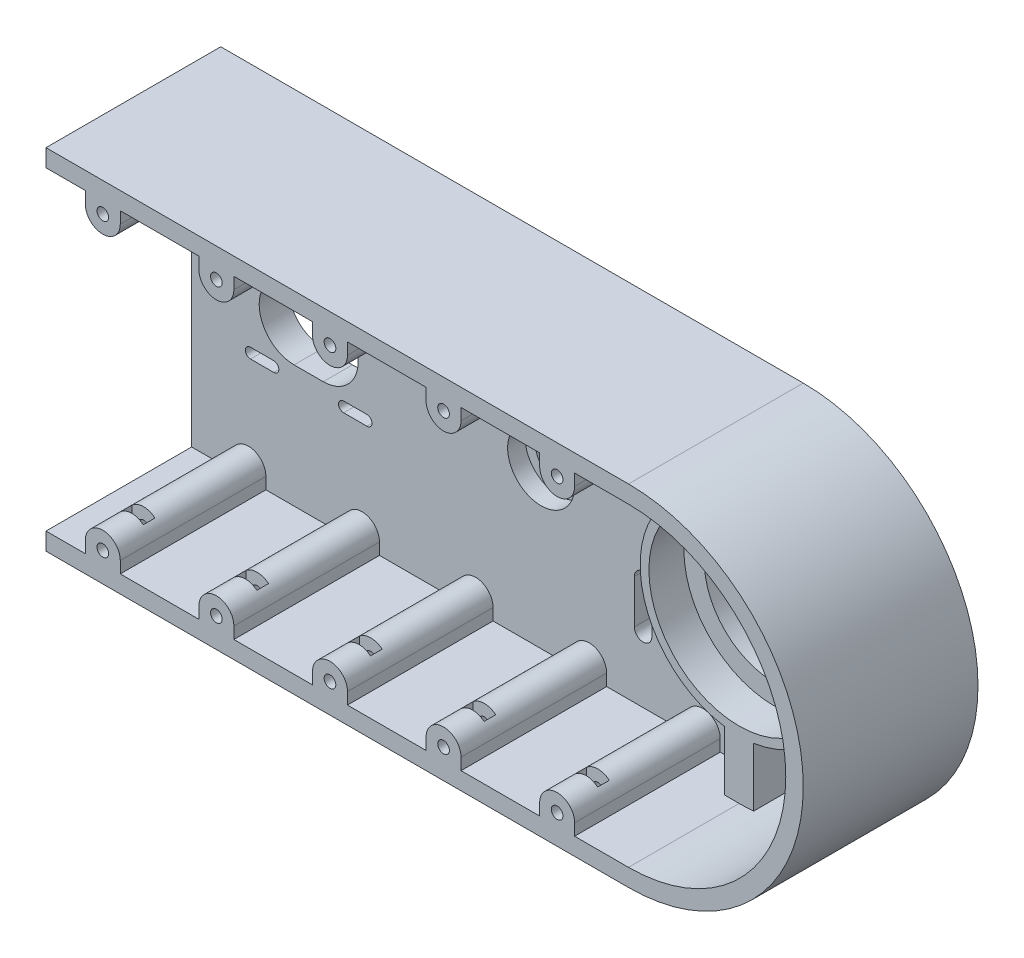
SolidWorks part; units mm, degrees
other "Marcação1"
sketch "Esboço6" plane through (60, -60, 0) normal (0.0064, -0.8941, -0.4477) x (-0.9984, -0.0306, 0.047)
sketch "Esboço8" plane through (60, -60, 0) normal (0.0064, -0.8941, -0.4477) x (-0.9984, -0.0306, 0.047)
sketch "Esboço13" plane through (60, -60, 0) normal (0.0064, -0.8941, -0.4477) x (-0.9984, -0.0306, 0.047)
sketch "Esboço15" plane through (60, -60, 0) normal (0.0064, -0.8941, -0.4477) x (-0.9984, -0.0306, 0.047)
ref_plane "Plano frontal" through (0, 0, 0) normal (0, 0, 1) x (1, 0, 0)
ref_plane "Plano superior" through (0, 0, 0) normal (0, 1, 0) x (1, 0, 0)
ref_plane "Plano direito" through (0, 0, 0) normal (1, 0, 0) x (0, 0, -1)
sketch "Esboço2" plane through (0, 0, 0) normal (0, 0, 1) x (1, 0, 0)
  line L0 (0, 60) -> (-200, 60)
  line L1 (-200, 60) -> (-200, -60)
  line L2 (-200, -60) -> (0, -60)
  circle A0 centre (0, 0) radius 19
  arc A1 (0, -60) -> (0, 60) centre (0, 0) ccw
  dimension "D1" = 38
  dimension "D2" = 120
  dimension "D3" = 200
extrude "Ressalto-extrusão1" add sketch "Esboço2" along normal blind 10
sketch "Esboço3" plane through (0, 0, 10) normal (0, 0, 1) x (1, 0, 0)
  circle A0 centre (0, 0) radius 24
  dimension "D1" = 48
extrude "Corte-extrusão1" cut sketch "Esboço3" against normal blind 7
sketch "Esboço4" plane through (0, 0, 10) normal (0, 0, 1) x (1, 0, 0)
  circle A0 centre (0, 0) radius 31
  circle A1 centre (0, 0) radius 34
  dimension "D1" = 62
  dimension "D2" = 68
extrude "Ressalto-extrusão2" add sketch "Esboço4" along normal blind 12
sketch "Esboço5" plane through (0, 0, 10) normal (0, 0, 1) x (1, 0, 0)
  line L0 (-200, 60) -> (0, 60)
  line L1 (-200, -60) -> (0, -60)
  line L2 (-200, 60) -> (-200, 54)
  line L3 (-200, 60) -> (-200, -60) construction
  line L4 (-200, -60) -> (-200, -54)
  line L5 (-200, 54) -> (0, 54)
  line L6 (-200, -54) -> (0, -54)
  arc A0 (0, -60) -> (0, 60) centre (0, 0) ccw
  arc A2 (0, -54) -> (0, 54) centre (0, 0) ccw
  dimension "D1" = 6
extrude "Ressalto-extrusão3" add sketch "Esboço5" along normal blind 50
sketch "Esboço7" plane through (0, 0, 0) normal (0, 0, -1) x (-1, 0, 0)
  line L0 (0, 60) -> (200, 60) construction
  line L1 (143.82, 15.99) -> (175.8, 15.99) construction
  line L2 (143.82, 15.99) -> (143.82, -15.99) construction
  line L3 (143.82, -15.99) -> (175.8, -15.99) construction
  line L4 (175.8, 15.99) -> (175.8, -15.99) construction
  line L5 (200, 60) -> (200, -60) construction
  line L6 (143.82, -15.99) -> (175.8, 15.99) construction
  line L7 (143.82, 15.99) -> (175.8, -15.99) construction
  line L8 (147.82, 15.99) -> (139.82, 15.99) construction
  line L9 (147.82, 14.24) -> (139.82, 14.24)
  line L10 (147.82, 17.74) -> (139.82, 17.74)
  line L11 (179.8, 17.74) -> (171.8, 17.74)
  line L12 (179.8, 14.24) -> (171.8, 14.24)
  line L13 (179.8, 15.99) -> (171.8, 15.99) construction
  line L14 (179.8, -17.74) -> (171.8, -17.74)
  line L15 (179.8, -14.24) -> (171.8, -14.24)
  line L16 (147.82, -14.24) -> (139.82, -14.24)
  line L17 (147.82, -17.74) -> (139.82, -17.74)
  line L18 (147.82, -15.99) -> (139.82, -15.99) construction
  line L19 (179.8, -15.99) -> (171.8, -15.99) construction
  line L20 (164.81, 0) -> (154.81, 0) construction
  line L21 (164.81, -12) -> (154.81, -12)
  line L22 (164.81, 12) -> (154.81, 12)
  arc A6 (147.82, 14.24) -> (147.82, 17.74) centre (147.82, 15.99) ccw
  arc A7 (139.82, 17.74) -> (139.82, 14.24) centre (139.82, 15.99) ccw
  arc A8 (179.8, 14.24) -> (179.8, 17.74) centre (179.8, 15.99) ccw
  arc A9 (171.8, 17.74) -> (171.8, 14.24) centre (171.8, 15.99) ccw
  arc A10 (171.8, -14.24) -> (171.8, -17.74) centre (171.8, -15.99) ccw
  arc A11 (179.8, -17.74) -> (179.8, -14.24) centre (179.8, -15.99) ccw
  arc A12 (147.82, -17.74) -> (147.82, -14.24) centre (147.82, -15.99) ccw
  arc A13 (139.82, -14.24) -> (139.82, -17.74) centre (139.82, -15.99) ccw
  arc A14 (164.81, -12) -> (164.81, 12) centre (164.81, 0) ccw
  arc A15 (154.81, 12) -> (154.81, -12) centre (154.81, 0) ccw
  point P10 (175.8, 0)
  point P17 (159.81, 0)
  point P19 (143.82, 15.99)
  point P24 (175.8, 15.99)
  point P33 (143.82, -15.99)
  point P38 (175.8, -15.99)
  dimension "D2" = 2
  dimension "D6" = 1.75
  dimension "D9" = 12
  dimension "D1" = 31.98
  dimension "D3" = 60
  dimension "D4" = 24.2
  dimension "D7" = 8
  dimension "D10" = 10
  dimension "D8" = 2
extrude "Corte-extrusão2" cut sketch "Esboço7" against normal up to surface (10 mm away) up to face at (34, 0, 10)
sketch "Esboço9" plane through (0, 0, 10) normal (0, 0, 1) x (1, 0, 0)
  line L0 (0, 0) -> (-200, 0) construction
  line L1 (-200, 54) -> (-200, -54) construction
  circle A0 centre (-80, 0) radius 11.5
  circle A1 centre (0, 0) radius 19 construction
  point P12 (-200, 0)
  dimension "D1" = 23
  dimension "D2" = 80
extrude "Corte-extrusão3" cut sketch "Esboço9" against normal blind 6 contours A0
sketch "Esboço10" plane through (0, 0, 4) normal (0, 0, 1) x (1, 0, 0)
  circle A0 centre (-80, 0) radius 8
  dimension "D1" = 16
extrude "Corte-extrusão4" cut sketch "Esboço10" against normal up to surface (4 mm away) up to face at (-175.8, -15.99, 0)
sketch "Esboço11" plane through (0, 0, 22) normal (0, 0, 1) x (1, 0, 0)
  line L0 (0, 34) -> (0, 60)
  line L1 (60, 0) -> (34, 0)
  line L2 (0, -34) -> (0, -60)
  circle A0 centre (0, 0) radius 34 construction
  circle A1 centre (0, 0) radius 34 construction
  arc A5 (0, -60) -> (0, 60) centre (0, 0) ccw construction
rib "Nervura1" sketch "Esboço11" sketch "Esboço11" thickness 10 extrusion direction normal to sketch draft on no parameters "D1"=10
sketch "Esboço12" plane through (0, 0, 10) normal (0, 0, 1) x (1, 0, 0)
  line L0 (-45, -16.5) -> (-45, -31.5) construction
  line L1 (-42, -16.5) -> (-42, -31.5)
  line L2 (-48, -16.5) -> (-48, -31.5)
  line L3 (-5, -54) -> (-200, -54) construction
  line L4 (0, 60) -> (-200, 60) construction
  line L5 (-200, 54) -> (-200, -54) construction
  arc A0 (-42, -16.5) -> (-48, -16.5) centre (-45, -16.5) ccw
  arc A1 (-48, -31.5) -> (-42, -31.5) centre (-45, -31.5) ccw
  circle A2 centre (-52, 20) radius 1.5
  circle A3 centre (-42.5, 20) radius 1.5
  point P2 (-45, -24)
  dimension "D1" = 3
  dimension "D5" = 3
  dimension "D6" = 3
  dimension "D7" = 9.5
  dimension "D8" = 40
  dimension "D9" = 148
  dimension "D2" = 15
  dimension "D3" = 30
  dimension "D4" = 45
extrude "Corte-extrusão5" cut sketch "Esboço12" against normal up to surface (10 mm away) up to face at (19, 0, 0)
sketch "Esboço14" plane through (0, 0, 10) normal (0, 0, 1) x (1, 0, 0)
  line L0 (-5, 50) -> (-200, 50) construction
  line L1 (-5, 54) -> (-5, 33.6303) construction
  line L2 (-200, 54) -> (-200, -54) construction
  line L3 (-200, 54) -> (0, 54) construction
  line L4 (-186.5, 50) -> (-186.5, 55)
  line L5 (-186.5, 55) -> (-174.5, 55)
  line L6 (-174.5, 55) -> (-174.5, 50)
  line L7 (-135.5, 55) -> (-135.5, 50)
  line L8 (-147.5, 55) -> (-135.5, 55)
  line L9 (-147.5, 50) -> (-147.5, 55)
  line L10 (-96.5, 55) -> (-96.5, 50)
  line L11 (-108.5, 55) -> (-96.5, 55)
  line L12 (-108.5, 50) -> (-108.5, 55)
  line L13 (-57.5, 55) -> (-57.5, 50)
  line L14 (-69.5, 55) -> (-57.5, 55)
  line L15 (-69.5, 50) -> (-69.5, 55)
  line L16 (-18.5, 55) -> (-18.5, 50)
  line L17 (-30.5, 55) -> (-18.5, 55)
  line L18 (-30.5, 50) -> (-30.5, 55)
  line L19 (33, 0) -> (-33, 0) construction
  line L20 (-30.5, -50) -> (-30.5, -55)
  line L21 (-30.5, -55) -> (-18.5, -55)
  line L22 (-18.5, -55) -> (-18.5, -50)
  line L23 (-69.5, -50) -> (-69.5, -55)
  line L24 (-69.5, -55) -> (-57.5, -55)
  line L25 (-57.5, -55) -> (-57.5, -50)
  line L26 (-108.5, -50) -> (-108.5, -55)
  line L27 (-108.5, -55) -> (-96.5, -55)
  line L28 (-96.5, -55) -> (-96.5, -50)
  line L29 (-147.5, -50) -> (-147.5, -55)
  line L30 (-147.5, -55) -> (-135.5, -55)
  line L31 (-135.5, -55) -> (-135.5, -50)
  line L32 (-174.5, -55) -> (-174.5, -50)
  line L33 (-186.5, -55) -> (-174.5, -55)
  line L34 (-186.5, -50) -> (-186.5, -55)
  arc A0 (-186.5, 50) -> (-174.5, 50) centre (-180.5, 50) ccw
  circle A1 centre (-180.5, 50) radius 2
  arc A2 (-147.5, 50) -> (-135.5, 50) centre (-141.5, 50) ccw
  circle A3 centre (-141.5, 50) radius 2
  arc A4 (-108.5, 50) -> (-96.5, 50) centre (-102.5, 50) ccw
  circle A5 centre (-102.5, 50) radius 2
  arc A6 (-69.5, 50) -> (-57.5, 50) centre (-63.5, 50) ccw
  circle A7 centre (-63.5, 50) radius 2
  arc A8 (-30.5, 50) -> (-18.5, 50) centre (-24.5, 50) ccw
  circle A9 centre (-24.5, 50) radius 2
  circle A10 centre (-24.5, -50) radius 2
  arc A11 (-30.5, -50) -> (-18.5, -50) centre (-24.5, -50) cw
  circle A12 centre (-63.5, -50) radius 2
  arc A13 (-69.5, -50) -> (-57.5, -50) centre (-63.5, -50) cw
  circle A14 centre (-102.5, -50) radius 2
  arc A15 (-108.5, -50) -> (-96.5, -50) centre (-102.5, -50) cw
  circle A16 centre (-141.5, -50) radius 2
  arc A17 (-147.5, -50) -> (-135.5, -50) centre (-141.5, -50) cw
  circle A18 centre (-180.5, -50) radius 2
  arc A19 (-186.5, -50) -> (-174.5, -50) centre (-180.5, -50) cw
  dimension "D2" = 19.5
  dimension "D3" = 4
  dimension "D4" = 12
  dimension "D1" = 4
  dimension "D5" = 5
  dimension "D6" = 5
extrude "Ressalto-extrusão5" add sketch "Esboço14" along normal up to surface (50 mm away) up to face at (-85.75, 0, 60)
ref_plane "Plano1" through (0, 0, 50) normal (0, 0, 1) x (1, 0, 0)
sketch "Esboço16" plane through (0, 0, 50) normal (0, 0, 1) x (1, 0, 0)
  line L0 (-186.5, 54) -> (-186.5, 50) construction
  line L1 (-184.4, 52.2517) -> (-184.4, 47.7483)
  line L4 (-176.6, 47.7483) -> (-176.6, 52.2517)
  line L5 (-176.6, 52.2517) -> (-180.5, 54.5033)
  line L6 (-180.5, 54.5033) -> (-184.4, 52.2517)
  line L7 (-184.4, 44) -> (-176.6, 44)
  line L8 (-176.6, 44) -> (-176.6, 47.7483)
  line L9 (-184.4, 44) -> (-184.4, 47.7483)
  line L10 (-145.4, 52.2517) -> (-145.4, 47.7483)
  line L11 (-182.45, 46.6225) -> (-180.5, 45.4967) [skipped]
  line L12 (-178.55, 46.6225) -> (-176.6, 47.7483) [skipped]
  line L13 (-141.5, 54.5033) -> (-145.4, 52.2517)
  line L14 (-137.6, 52.2517) -> (-141.5, 54.5033)
  line L15 (-137.6, 47.7483) -> (-137.6, 52.2517)
  line L16 (-137.6, 44) -> (-137.6, 47.7483)
  line L17 (-145.4, 44) -> (-145.4, 47.7483)
  line L18 (-145.4, 44) -> (-137.6, 44)
  line L19 (-106.4, 52.2517) -> (-106.4, 47.7483)
  line L20 (-102.5, 54.5033) -> (-106.4, 52.2517)
  line L21 (-98.6, 52.2517) -> (-102.5, 54.5033)
  line L22 (-98.6, 47.7483) -> (-98.6, 52.2517)
  line L23 (-98.6, 44) -> (-98.6, 47.7483)
  line L24 (-106.4, 44) -> (-106.4, 47.7483)
  line L25 (-106.4, 44) -> (-98.6, 44)
  line L26 (-67.4, 52.2517) -> (-67.4, 47.7483)
  line L27 (-63.5, 54.5033) -> (-67.4, 52.2517)
  line L28 (-59.6, 52.2517) -> (-63.5, 54.5033)
  line L29 (-59.6, 47.7483) -> (-59.6, 52.2517)
  line L30 (-59.6, 44) -> (-59.6, 47.7483)
  line L31 (-67.4, 44) -> (-67.4, 47.7483)
  line L32 (-67.4, 44) -> (-59.6, 44)
  line L33 (-28.4, 52.2517) -> (-28.4, 47.7483)
  line L34 (-24.5, 54.5033) -> (-28.4, 52.2517)
  line L35 (-20.6, 52.2517) -> (-24.5, 54.5033)
  line L36 (-20.6, 47.7483) -> (-20.6, 52.2517)
  line L37 (-20.6, 44) -> (-20.6, 47.7483)
  line L38 (-28.4, 44) -> (-28.4, 47.7483)
  line L39 (-28.4, 44) -> (-20.6, 44)
  line L40 (33, 0) -> (-33, 0) construction
  line L41 (-28.4, -44) -> (-20.6, -44)
  line L42 (-28.4, -44) -> (-28.4, -47.7483)
  line L43 (-20.6, -44) -> (-20.6, -47.7483)
  line L44 (-20.6, -47.7483) -> (-20.6, -52.2517)
  line L45 (-20.6, -52.2517) -> (-24.5, -54.5033)
  line L46 (-24.5, -54.5033) -> (-28.4, -52.2517)
  line L47 (-28.4, -52.2517) -> (-28.4, -47.7483)
  line L48 (-67.4, -44) -> (-59.6, -44)
  line L49 (-67.4, -44) -> (-67.4, -47.7483)
  line L50 (-59.6, -44) -> (-59.6, -47.7483)
  line L51 (-59.6, -47.7483) -> (-59.6, -52.2517)
  line L52 (-59.6, -52.2517) -> (-63.5, -54.5033)
  line L53 (-63.5, -54.5033) -> (-67.4, -52.2517)
  line L54 (-67.4, -52.2517) -> (-67.4, -47.7483)
  line L55 (-106.4, -44) -> (-98.6, -44)
  line L56 (-106.4, -44) -> (-106.4, -47.7483)
  line L57 (-98.6, -44) -> (-98.6, -47.7483)
  line L58 (-98.6, -47.7483) -> (-98.6, -52.2517)
  line L59 (-98.6, -52.2517) -> (-102.5, -54.5033)
  line L60 (-102.5, -54.5033) -> (-106.4, -52.2517)
  line L61 (-106.4, -52.2517) -> (-106.4, -47.7483)
  line L62 (-145.4, -44) -> (-137.6, -44)
  line L63 (-145.4, -44) -> (-145.4, -47.7483)
  line L64 (-137.6, -44) -> (-137.6, -47.7483)
  line L65 (-137.6, -47.7483) -> (-137.6, -52.2517)
  line L66 (-137.6, -52.2517) -> (-141.5, -54.5033)
  line L67 (-141.5, -54.5033) -> (-145.4, -52.2517)
  line L68 (-145.4, -52.2517) -> (-145.4, -47.7483)
  line L69 (-184.4, -44) -> (-184.4, -47.7483)
  line L70 (-176.6, -44) -> (-176.6, -47.7483)
  line L71 (-184.4, -44) -> (-176.6, -44)
  line L72 (-180.5, -54.5033) -> (-184.4, -52.2517)
  line L73 (-176.6, -52.2517) -> (-180.5, -54.5033)
  line L74 (-176.6, -47.7483) -> (-176.6, -52.2517)
  line L75 (-184.4, -52.2517) -> (-184.4, -47.7483)
  circle A0 centre (-180.5, 50) radius 3.9 construction
  circle A1 centre (-180.5, -50) radius 3.9 construction
  point P14 (-180.5, 44)
  point P84 (-180.5, -44)
  dimension "D1" = 7.8
  dimension "D2" = 10.5033
  dimension "D3" = 5
extrude "Corte-extrusão6" cut sketch "Esboço16" against normal blind 4
